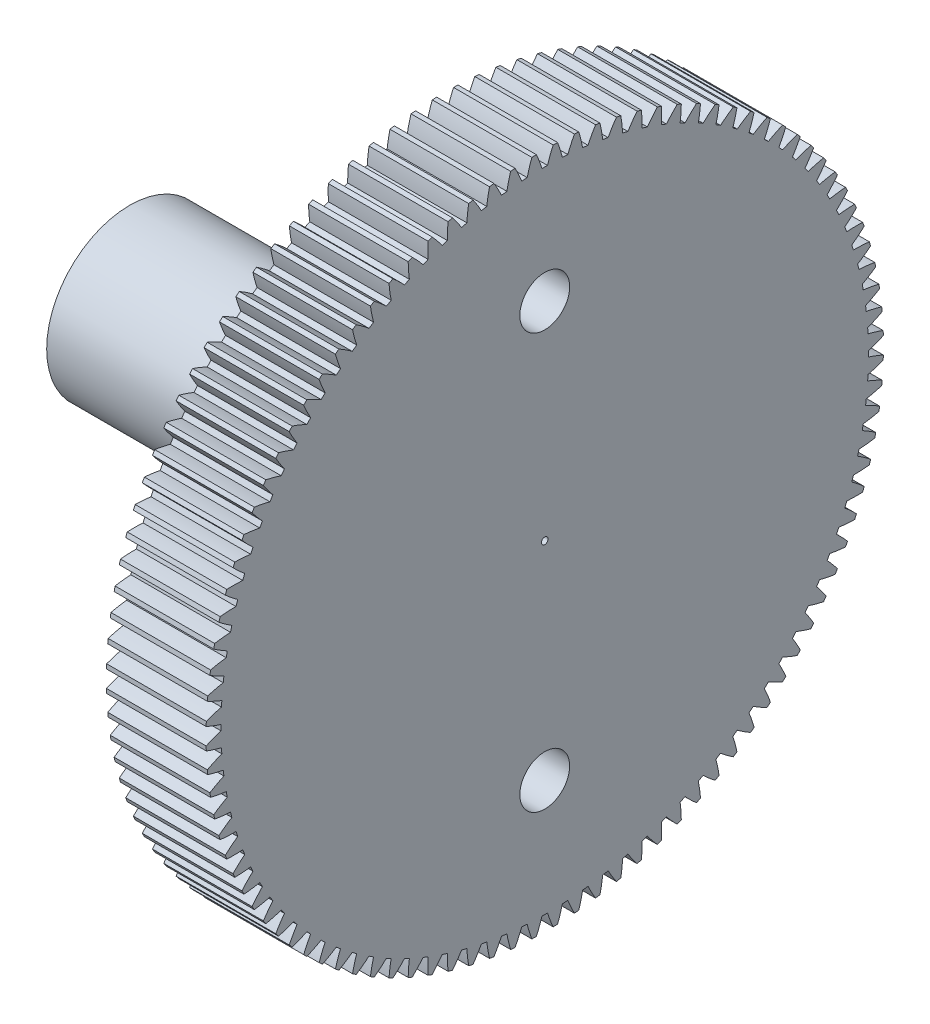
SolidWorks part; units mm, degrees
ref_plane "Plane1" through (0, 0, 0) normal (0, 0, 1) x (1, 0, 0)
ref_plane "Plane2" through (0, 0, 0) normal (0, 1, 0) x (1, 0, 0)
ref_plane "Plane3" through (0, 0, 0) normal (1, 0, 0) x (0, 0, -1)
other "Configuration Table"
sketch "HoldingSke" plane through (0, 0, 0) normal (0, 1, 0) x (1, 0, 0)
  line L0 (0, 0) -> (-0.2171, -1.231)
  line L1 (-15, 0) -> (100, 0) construction
  line L2 (0, 0) -> (-2.1039, 2.3779)
  line L3 (0, 0) -> (-11.863, 4.5341)
  line L4 (0, 0) -> (-1.4996, 8.5048)
  line L5 (0, 0) -> (-46.8476, -17.4728)
  line L6 (0, 0) -> (-9.9476, -6.7116)
  line L7 (-2.1039, 2.3779) -> (8.6586, 51.2059)
  line L8 (-76.2, 54.61) -> (-76.1, 54.61)
  line L9 (-71.009, 38.7566) -> (-53.1078, 45.2721)
  line L10 (-76.2, 71.12) -> (104.1128, 71.12)
  line L11 (0, 0) -> (-12, 0)
  line L12 (-76.2, 101.6) -> (-76.17, 101.6)
  line L13 (24.9733, 27.94) -> (52.9518, 28.4284)
  line L14 (24.9733, 27.94) -> (24.9743, 27.94)
  line L15 (24.9733, 27.94) -> (100.4006, 29.5858)
  line L16 (-63.627, -0.8) -> (-12.827, -0.8)
  circle A0 centre (0, 0) radius 0.4
  circle A1 centre (0, 0) radius 10
  circle A2 centre (0, 0) radius 10
  circle A3 centre (0, 0) radius 0.4
  dimension "Num_teeth" = 100
  dimension "Pitch_radius" = 180.3128
  dimension "Width" = 12
  dimension "Thickness" = 12
sketch "BasProSke" plane through (0, 0, 0) normal (0, 1, 0) x (1, 0, 0)
  line L0 (-10, 0) -> (60, 0) construction
  line L1 (0, 0) -> (0, 40.8)
  line L2 (0, 0) -> (12, 0)
  line L3 (12, 0) -> (12, 40.8)
  line L4 (12, 40.8) -> (0, 40.8)
  dimension "Thickness" = 12
  dimension "Diameter" = 81.6
revolve "Base-Revolve" add sketch "BasProSke" angle 360 about L0
sketch "TooCutSke" plane through (0, 0, 0) normal (1, 0, 0) x (0, 0, -1)
  line L1 (0, 0) -> (0, 107) construction
  line L2 (0, 0) -> (-0.6808, 39.9942) construction
  line L3 (0, 0) -> (-2.5126, 79.9522) construction
  line L4 (-0.6808, 39.9942) -> (-1.2563, 39.9761) construction
  arc A0 (0.331, 38.9976) -> (-0.331, 38.9976) centre (0, 0) ccw
  arc A1 (1.0251, 40.8125) -> (-1.0251, 40.8125) centre (0, 0) ccw
  circle A2 centre (0, 0) radius 40 construction
  circle A3 centre (0, 0) radius 37.5877 construction
  arc A4 (-0.331, 38.9976) -> (-1.0251, 40.8125) centre (-15.5948, 34.2) ccw
  arc A5 (1.0251, 40.8125) -> (0.331, 38.9976) centre (15.5948, 34.2) ccw
extrude "ToothCut" cut sketch "TooCutSke" along normal through all
fillet "Breaks" [suppressed] radius 0.016 tangent propagation no
fillet "RootFillets" [suppressed] radius 0.201
pattern_circular "TeethCuts" count 100 every 3.6 about axis through (-10, 0, 0) along (1, 0, 0) of "ToothCut", "RootFillets", "Breaks"
sketch "HubNeaOneSke" plane through (0, 0, 0) normal (-1, 0, 0) x (0, 0, 1)
  circle A0 centre (0, 0) radius 10
  dimension "Diameter" = 20
extrude "HubNearOne" add sketch "HubNeaOneSke" along normal blind 38.0001
sketch "HubNeaBotSke" plane through (0, 0, 0) normal (-1, 0, 0) x (0, 0, 1)
  circle A0 centre (0, 0) radius 10
  dimension "Diameter" = 20
extrude "HubNearBoth" [suppressed] add sketch "HubNeaBotSke" along normal blind 19
ref_plane "FarPln" through (12, 0, 0) normal (1, 0, 0) x (0, 0, -1)
sketch "HubFarSke" plane through (12, 0, 0) normal (1, 0, 0) x (0, 0, -1)
  circle A0 centre (0, 0) radius 10
  dimension "Diameter" = 20
extrude "HubFar" [suppressed] add sketch "HubFarSke" along normal blind 19
sketch "BorSke" plane through (0, 0, 0) normal (1, 0, 0) x (0, 0, -1)
  circle A0 centre (0, 0) radius 0.4
  dimension "Diameter" = 0.8
extrude "Bore" cut sketch "BorSke" along normal mid plane 100.0001
sketch "KeySke" plane through (0, 0, 0) normal (1, 0, 0) x (0, 0, -1)
  line L0 (-0.05, 0) -> (-0.05, 0.5)
  line L1 (-0.05, 0.5) -> (0.05, 0.5)
  line L2 (0.05, 0.5) -> (0.05, 0)
  line L3 (0, 0) -> (0, 34) construction
  line L4 (-0.05, 0) -> (0.05, 0)
  dimension "Width" = 0.1
extrude "Keyway" [suppressed] cut sketch "KeySke" along normal mid plane 100.0001
pattern_circular "Keyway2" [suppressed] count 2 every 90 about axis through (-10, 0, 0) along (1, 0, 0) reverse direction yes
sketch "Sketch1" plane through (12, 0, 0) normal (1, 0, 0) x (0, 0, -1)
  line L0 (0, 42.6862) -> (0, -42.1037) construction
  circle A0 centre (0, 25) radius 3
  circle A1 centre (0, 0) radius 0.4 construction
  circle A2 centre (0, -25) radius 3
  dimension "D1" = 6
  dimension "D2" = 25
  dimension "D3" = 0.0001
  dimension "D4" = 2
extrude "Cut-Extrude1" cut sketch "Sketch1" against normal blind 20
equation "' \"Module@HoldingSke\" = 6.35"
equation "' \"Num_teeth@HoldingSke\" = 12"
equation "' \"Ap@HoldingSke\" =  20"
equation "' \"Ap@HoldingSke\" = 20"
equation "' \"Width@HoldingSke\" = 0.5 * 25.4"
equation "' \"Hub_dia@HoldingSke\"= 1 * 25.4"
equation "' \"Hub_dia@HoldingSke\" = 1 * 25.4"
equation "' \"Overall_len@HoldingSke\" = 1.0 * 25.4"
equation "' \"Bore@HoldingSke\" = 0.75 * 25.4"
equation "' \"T_dim@HoldingSke\" = 0.1 * 25.4"
equation "' \"Width@KeySke\" = 0.25 * 25.4"
equation "' \"Show_teeth@HoldingSke\" = 13"
equation "' \"Backlash@HoldingSke\" = 0.009 * 25.4"
equation "' \"Addendum_fac@HoldingSke\" = 1.0"
equation "' \"Dedendum_fac@HoldingSke\" = 1.25"
equation "' \"Dedendum_add@HoldingSke\" = 0.00005 * 25.4"
equation "' \"Clearance_fac@HoldingSke\" = 0.25"
equation "\"Pitch@HoldingSke\" = 1 / \"Module@HoldingSke\""
equation "\"Overcut_dia@TooCutSke\" = (\"Num_teeth@HoldingSke\" + 2 * \"Addendum_fac@HoldingSke\") / \"Pitch@HoldingSke\" + 0.002 * 25.4"
equation "\"Pitch_dia@TooCutSke\" = \"Num_teeth@HoldingSke\" / \"Pitch@HoldingSke\""
equation "\"Base_dia@TooCutSke\" = \"Num_teeth@HoldingSke\" / \"Pitch@HoldingSke\" * cos((\"Ap@HoldingSke\"  * 3.14159265 / 180))"
equation "\"Root_dia@TooCutSke\" = (\"Num_teeth@HoldingSke\" + 2) / \"Pitch@HoldingSke\" - 2 * (\"Addendum_fac@HoldingSke\" + \"Dedendum_fac@HoldingSke\") / \"Pitch@HoldingSke\" - \"Dedendum_add@HoldingSke\" * 2"
equation "\"Half_ang@TooCutSke\" = 180 / \"Num_teeth@HoldingSke\""
equation "\"Half_CT@TooCutSke\" = \"Num_teeth@HoldingSke\" / \"Pitch@HoldingSke\" * sin((3.14159265 / 2 / \"Num_teeth@HoldingSke\")) / 2 - 7 * \"Backlash@HoldingSke\" / 4"
equation "\"Flank_rad@TooCutSke\" = \"Num_teeth@HoldingSke\" / \"Pitch@HoldingSke\" / 5"
equation "\"Radius@RootFillets\" = \"Clearance_fac@HoldingSke\" / \"Pitch@HoldingSke\" + \"Dedendum_add@HoldingSke\""
equation "\"Break_rad@Breaks\" = 0.02 / \"Pitch@HoldingSke\""
equation "\"Thickness@HoldingSke\" = \"Width@HoldingSke\""
equation "\"OAL@HoldingSke\" = \"Thickness@HoldingSke\""
equation "\"MHD@HoldingSke\" = (\"Num_teeth@HoldingSke\" + 2) / \"Pitch@HoldingSke\" - 2 * (\"Addendum_fac@HoldingSke\" + \"Dedendum_fac@HoldingSke\")  / \"Pitch@HoldingSke\" - \"Dedendum_add@HoldingSke\" * 2"
equation "\"MBD@HoldingSke\" = (\"Num_teeth@HoldingSke\" + 2) / \"Pitch@HoldingSke\" - 2 * (\"Addendum_fac@HoldingSke\" + \"Dedendum_fac@HoldingSke\")  / \"Pitch@HoldingSke\" - \"Dedendum_add@HoldingSke\" * 2 - 0.002 * 25.4"
equation "\"MHD@HoldingSke\" = ((sgn( \"MHD@HoldingSke\" - \"Hub_dia@HoldingSke\" )-1)*( \"MHD@HoldingSke\" - \"Hub_dia@HoldingSke\" ))/-2+ \"Hub_dia@HoldingSke\""
equation "\"MBD@HoldingSke\" = ((sgn( \"MBD@HoldingSke\" - \"Bore@HoldingSke\" )-1)*( \"MBD@HoldingSke\" - \"Bore@HoldingSke\" ))/-2+ \"Bore@HoldingSke\""
equation "\"OAL@HoldingSke\" = ((sgn( \"OAL@HoldingSke\" - \"Overall_len@HoldingSke\" )+1)*( \"OAL@HoldingSke\" - \"Overall_len@HoldingSke\" ))/2 + \"Overall_len@HoldingSke\" + 0.000002 * 25.4"
equation "\"Num_teeth@TeethCuts\" = int( \"Show_teeth@HoldingSke\" ) + 1"
equation "\"Num_teeth@TeethCuts\" = ((sgn( \"Num_teeth@TeethCuts\" - \"Num_teeth@HoldingSke\" )-1)*( \"Num_teeth@TeethCuts\" - \"Num_teeth@HoldingSke\" ))/-2+ \"Num_teeth@HoldingSke\""
equation "\"Num_teeth@TeethCuts\" = ((sgn( \"Num_teeth@TeethCuts\" - 2.0)+1)*( \"Num_teeth@TeethCuts\" - 2.0))/2 +2.0"
equation "\"Angle@TeethCuts\" = 360.0 / \"Num_teeth@HoldingSke\""
equation "\"Diameter@BasProSke\" = (\"Num_teeth@HoldingSke\" + 2 * \"Addendum_fac@HoldingSke\") / \"Pitch@HoldingSke\""
equation "\"Thickness@BasProSke\"  = \"Thickness@HoldingSke\""
equation "' \"Fillet_rad@BasProSke\" =  \"Thickness@HoldingSke\" * 0.05"
equation "' \"Fillet_rad@BasProSke\" = \"Thickness@HoldingSke\" * 0.05"
equation "\"MHD@HoldingSke\" = ((sgn( \"MHD@HoldingSke\" - \"Root_dia@TooCutSke\" )-1)*( \"MHD@HoldingSke\" - \"Root_dia@TooCutSke\" ))/-2+ \"Root_dia@TooCutSke\""
equation "\"Diameter@HubNeaOneSke\" = \"MHD@HoldingSke\""
equation "\"Length@HubNearOne\" = \"OAL@HoldingSke\" - \"Thickness@BasProSke\""
equation "\"Diameter@HubNeaBotSke\" = \"MHD@HoldingSke\""
equation "\"Length@HubNearBoth\" = ( \"OAL@HoldingSke\" - \"Thickness@BasProSke\" ) / 2.0"
equation "\"Thickness@FarPln\" = \"Thickness@BasProSke\""
equation "\"Diameter@HubFarSke\" = \"MHD@HoldingSke\""
equation "\"Length@HubFar\" = ( \"OAL@HoldingSke\" - \"Thickness@BasProSke\" ) / 2.0"
equation "\"Diameter@BorSke\" = \"MBD@HoldingSke\""
equation "\"D1@Bore\" = \"OAL@HoldingSke\" * 2.0"
equation "\"D1@Keyway\" = \"OAL@HoldingSke\" * 2.0"
equation "\"Offset@KeySke\" = \"T_dim@HoldingSke\" + \"MBD@HoldingSke\" / 2.0"
